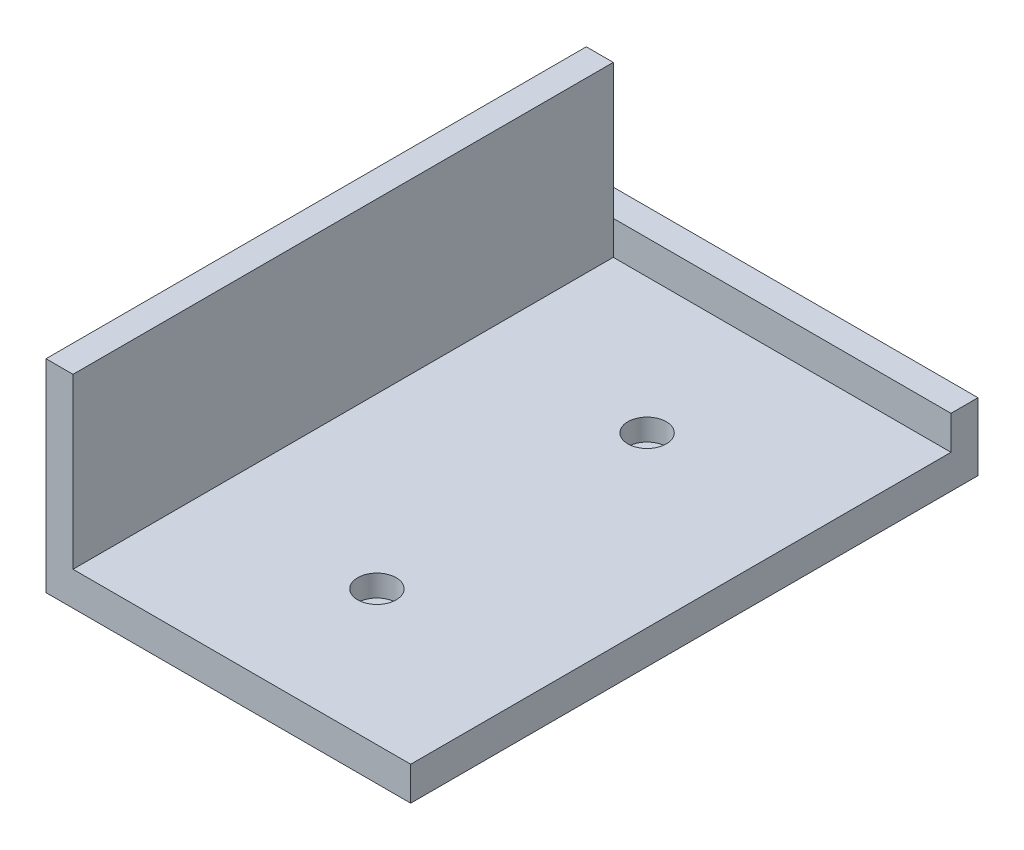
SolidWorks part; units mm, degrees
ref_plane "Ebene vorne" through (0, 0, 0) normal (0, 0, 1) x (1, 0, 0)
ref_plane "Ebene oben" through (0, 0, 0) normal (0, 1, 0) x (1, 0, 0)
ref_plane "Ebene rechts" through (0, 0, 0) normal (1, 0, 0) x (0, 0, -1)
sketch "Sketch1" plane through (0, 0, 0) normal (0, 1, 0) x (1, 0, 0)
  line L1 (-51.4953, 35.7632) -> (-1.4953, 35.7632)
  line L2 (-51.4953, 35.7632) -> (-51.4953, -44.2368)
  line L3 (-51.4953, -44.2368) -> (-1.4953, -44.2368)
  line L4 (-1.4953, 35.7632) -> (-1.4953, -44.2368)
  line L5 (-1.4953, 39.7632) -> (-55.4953, 39.7632)
  line L6 (-1.4953, 39.7632) -> (-1.4953, 35.7632)
  line L7 (-1.4953, 35.7632) -> (-55.4953, 35.7632)
  line L8 (-55.4953, 39.7632) -> (-55.4953, 35.7632)
  line L9 (-51.4953, 35.7632) -> (-55.4953, 35.7632)
  line L10 (-51.4953, 35.7632) -> (-51.4953, -44.2368)
  line L11 (-51.4953, -44.2368) -> (-55.4953, -44.2368)
  line L12 (-55.4953, 35.7632) -> (-55.4953, -44.2368)
  dimension "D1" = 80
  dimension "D2" = 4
  dimension "D3" = 4
  dimension "D4" = 50
extrude "Boss-Extrude1" add sketch "Sketch1" along normal blind 5 contours L4 L1 L2 L3 region at (-26.4953, 0, 4.2368)
extrude "Boss-Extrude2" add sketch "Sketch1<3>" along normal blind 10 contours L5 L8 L7 L1 L6 region at (-28.4953, 0, -37.7632)
sketch "Sketch1<3>" plane through (0, 0, 0) normal (0, 1, 0) x (1, 0, 0) same geometry as "Sketch1"
extrude "Boss-Extrude3" add sketch "Sketch1<4>" along normal blind 30 contours L7 L12 L11 L2 region at (-53.4953, 0, 4.2368)
sketch "Sketch1<4>" plane through (0, 0, 0) normal (0, 1, 0) x (1, 0, 0) same geometry as "Sketch1"
hole_wizard "CBORE for M5 Hex Head Bolt1" positions "Sketch2" profile "Sketch3" counterbore size "M5" standard "ANSI Metric" end condition through all
sketch "Sketch2" plane through (-25.6654, 5, -85) normal (0, 1, 0) x (1, 0, 0)
  line L2 (-0.83, -129.2368) -> (-0.83, -49.2368) construction
  point P0 (-0.83, -69.2368)
  point P1 (-0.83, -109.2368)
sketch "Sketch3" plane through (-26.4953, 5, -15.7632) normal (1, 0, 0) x (0, 0, 1)
  line L0 (0, 0) -> (0, 5)
  line L1 (0, 5) -> (1.5, 5)
  line L3 (1.5, 5) -> (1.5, 3.2)
  line L4 (1.5, 3.2) -> (2.85, 3.2)
  line L5 (2.85, 3.2) -> (2.85, 0)
  line L7 (2.85, 0) -> (0, 0)
  line L11 (0, -6.35) -> (0, 107.95) construction
  dimension "Thru Hole Dia." = 3
  dimension "Thru Hole Depth" = 5
  dimension "C'Bore Dia." = 5.7
  dimension "C'Bore Depth" = 3.2
